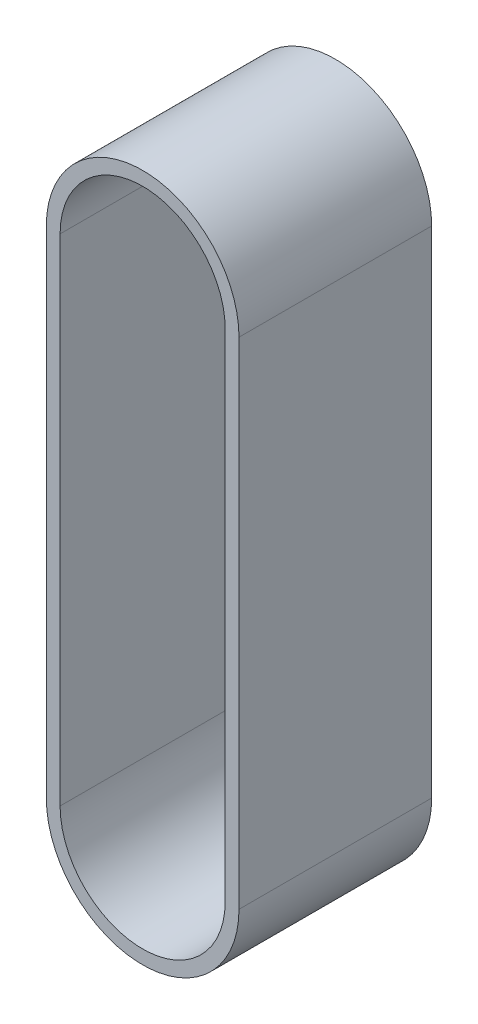
SolidWorks part; units mm, degrees
ref_plane "Front Plane" through (0, 0, 0) normal (0, 0, 1) x (1, 0, 0)
ref_plane "Top Plane" through (0, 0, 0) normal (0, 1, 0) x (1, 0, 0)
ref_plane "Right Plane" through (0, 0, 0) normal (1, 0, 0) x (0, 0, -1)
sketch "Sketch1" plane through (0, 0, 0) normal (0, 1, 0) x (1, 0, 0)
  line L1 (-35, -35) -> (35, -35)
  line L2 (-35, -35) -> (-35, 35)
  line L3 (-35, 35) -> (35, 35)
  line L4 (35, -35) -> (35, 35)
  line L5 (-35, -35) -> (35, 35) construction
  line L6 (-35, 35) -> (35, -35) construction
  point P0 (0, 0)
  dimension "D1" = 70
  dimension "D2" = 70
extrude "Boss-Extrude1" add sketch "Sketch1" along normal blind 250
sketch "Sketch2" plane through (0, 0, 35) normal (0, 0, 1) x (1, 0, 0)
  line L5 (-30, 215) -> (-30, 35)
  line L6 (30, 215) -> (30, 35)
  line L7 (-35, 215) -> (-35, 250)
  line L8 (-35, 250) -> (35, 250)
  line L9 (35, 250) -> (35, 215)
  line L10 (-35, 35) -> (-35, 0)
  line L11 (-35, 0) -> (35, 0)
  line L12 (35, 0) -> (35, 35)
  circle A2 centre (0, 215) radius 30
  circle A3 centre (0, 35) radius 30
  arc A4 (35, 215) -> (-35, 215) centre (0, 215) ccw
  arc A5 (-35, 35) -> (35, 35) centre (0, 35) ccw
  line M3 (-35, 0) -> (35, 0)
  line M4 (35, 0) -> (35, 250)
  line M5 (35, 250) -> (-35, 250)
  line M6 (-35, 250) -> (-35, 0)
extrude "Cut-Extrude2" cut sketch "Sketch2" against normal offset from surface (65 mm away) 5 contours A4 L8 M6 | A4 M4 M5 | A5 M6 M3 | A5 L11 M4 | A3 L6 A2 L5 | A2 | A3 region at (0, 125, 35) region at (0, 215, 35) region at (0, 35, 35) region at (-27.1821, 242.1821, 35) region at (27.1821, 242.1821, 35) region at (-27.1821, 7.8179, 35) region at (27.1821, 7.8179, 35) up to face at (0, 125, -35)
sketch "Sketch4" plane through (0, 0, -30) normal (0, 0, 1) x (1, 0, 0)
  line L0 (-35, 35) -> (-35, 0)
  line L1 (-35, 0) -> (35, 0)
  line L2 (35, 0) -> (35, 35)
  line L3 (-35, 215) -> (-35, 250)
  line L4 (-35, 250) -> (35, 250)
  line L5 (35, 250) -> (35, 215)
  circle A0 centre (0, 215) radius 35
  circle A1 centre (0, 35) radius 35
  circle A2 centre (0, 215) radius 5
  circle A3 centre (0, 35) radius 5
  line M2 (-35, 250) -> (-35, 215)
  arc M3 (-35, 215) -> (0, 250) centre (0, 215) cw
  line M4 (0, 250) -> (-35, 250)
extrude "Cut-Extrude3" cut sketch "Sketch4" against normal through all contours M4 M2 M3 | A0 L5 L4 | A1 L0 L1 | A1 L1 L2 | A2 | A3 region at (-27.1821, 7.8179, -30) region at (27.1821, 7.8179, -30) region at (-27.1821, 242.1821, -30) region at (27.1821, 242.1821, -30)
